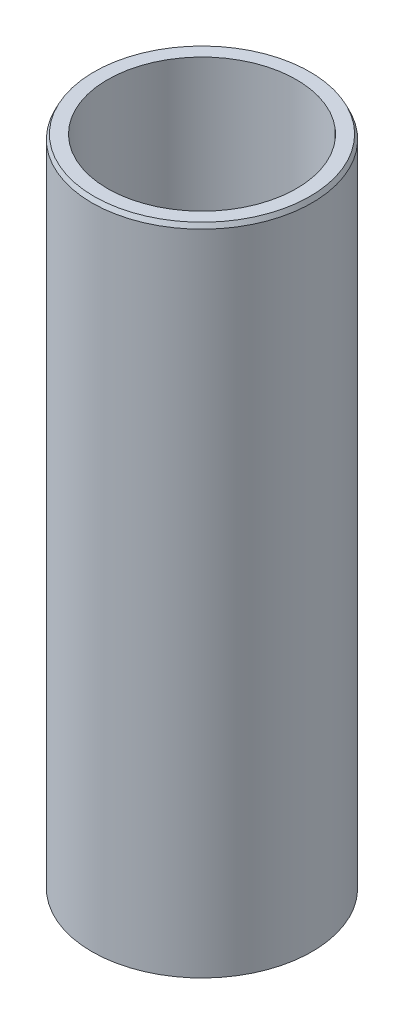
SolidWorks part; units mm, degrees
ref_plane "Front Plane" through (0, 0, 0) normal (0, 0, 1) x (1, 0, 0)
ref_plane "Top Plane" through (0, 0, 0) normal (0, 1, 0) x (1, 0, 0)
ref_plane "Right Plane" through (0, 0, 0) normal (1, 0, 0) x (0, 0, -1)
sketch "Sketch1" plane through (0, 0, 0) normal (0, 1, 0) x (1, 0, 0)
  circle A0 centre (0, 0) radius 57.5
  dimension "SHAFT_OD" = 115
extrude "Boss-Extrude1" add sketch "Sketch1" along normal blind 342.2317
sketch "Sketch2" plane through (0, 0, 0) normal (0, 1, 0) x (1, 0, 0)
  circle A0 centre (0, 0) radius 49.3284
  dimension "BORE_D" = 98.6569
extrude "Cut-Extrude1" cut sketch "Sketch2" along normal through all
chamfer "Chamfer1" distance 2.3666 angle 25.303 2 edges at (0, 342.2317, 57.5) (0, 0, 57.5) first distance on face at (0, 342.2317, 57.5) first distance on face at (0, 0, 49.3284)
